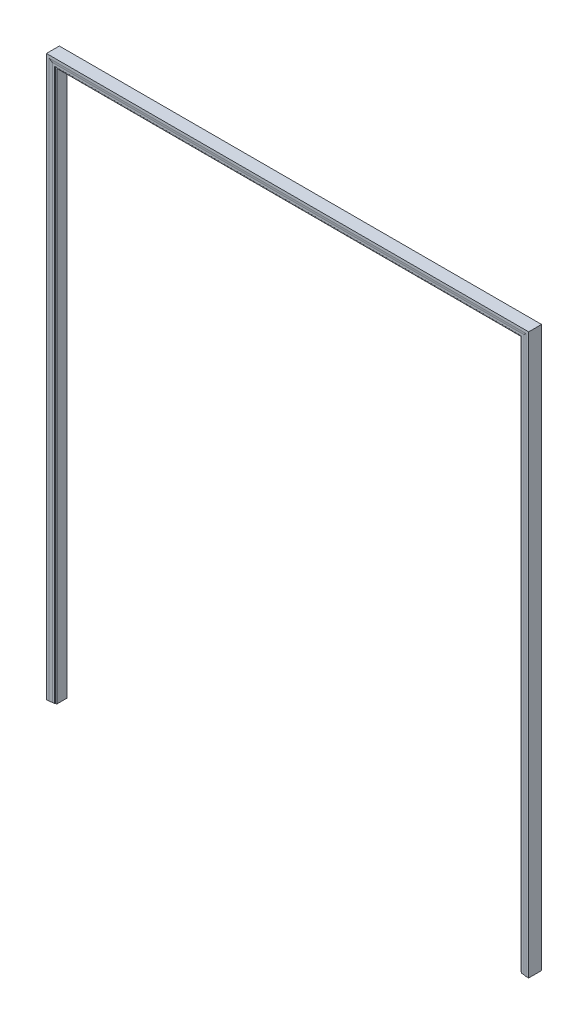
SolidWorks part; units mm, degrees
ref_plane "Front" through (0, 0, 0) normal (0, 0, 1) x (1, 0, 0)
ref_plane "Top" through (0, 0, 0) normal (0, 1, 0) x (1, 0, 0)
ref_plane "Right" through (0, 0, 0) normal (1, 0, 0) x (0, 0, -1)
sketch "Sketch1" plane through (0, 0, 0) normal (0, 0, 1) x (1, 0, 0)
  line L0 (-935, -1102.5) -> (-935, 1102.5)
  line L1 (-900, -1067.5) -> (900, -1067.5)
  line L2 (-900, -1067.5) -> (-900, 1067.5)
  line L3 (-900, 1067.5) -> (900, 1067.5)
  line L4 (900, -1067.5) -> (900, 1067.5)
  line L5 (-900, -1067.5) -> (900, 1067.5) construction
  line L6 (-900, 1067.5) -> (900, -1067.5) construction
  line L7 (-935, 1102.5) -> (935, 1102.5)
  line L8 (935, -1102.5) -> (935, 1102.5)
  line L9 (-935, -1102.5) -> (935, -1102.5)
  point P0 (0, 0)
  dimension "D1" = 2135
  dimension "D2" = 1800
  dimension "D3" = 35
extrude "Boss-Extrude1" add sketch "Sketch1" along normal mid plane 50
sketch "Sketch2" plane through (0, 0, 25) normal (0, 0, 1) x (1, 0, 0)
  line L8 (-905, -1072.5) -> (905, -1072.5)
  line L9 (905, -1072.5) -> (905, 1072.5)
  line L10 (905, 1072.5) -> (-905, 1072.5)
  line L11 (-905, 1072.5) -> (-905, -1072.5)
  line L12 (-905, -1072.5) -> (905, -1072.5)
  line L13 (905, -1072.5) -> (905, 1072.5)
  line L14 (905, 1072.5) -> (-905, 1072.5)
  line L15 (-905, 1072.5) -> (-905, -1072.5)
  dimension "D1" = 5
extrude "Cut-Extrude2" cut sketch "Sketch2" against normal blind 5
sketch "Sketch3" plane through (0, 0, 25) normal (0, 0, 1) x (1, 0, 0)
  line L8 (912.5, -1080) -> (912.5, 1080)
  line L9 (-912.5, -1080) -> (912.5, -1080)
  line L10 (-912.5, 1080) -> (-912.5, -1080)
  line L11 (912.5, 1080) -> (-912.5, 1080)
  line L12 (912.5, -1080) -> (912.5, 1080)
  line L13 (-912.5, -1080) -> (912.5, -1080)
  line L14 (-912.5, 1080) -> (-912.5, -1080)
  line L15 (912.5, 1080) -> (-912.5, 1080)
  dimension "D1" = 7.5
extrude "Cut-Extrude4" cut sketch "Sketch3" against normal blind 2
fillet "Fillet1" radius 1 4 edges at (905, 0, 23) (0, 1072.5, 23) (-905, 0, 23) (0, -1072.5, 23)
chamfer "Chamfer1" distance 12 angle 11 4 edges at (0, 1080, 25) (912.5, 0, 25) (0, -1080, 25) (-912.5, 0, 25) first distance on face at (0, 0, 25)
mirror "Mirror1" about plane through (0, 0, 0) normal (0, 0, 1) of "Cut-Extrude4", "Cut-Extrude2"
fillet "Fillet2" radius 1 4 edges at (-905, 0, -23) (0, -1072.5, -23) (905, 0, -23) (0, 1072.5, -23)
chamfer "Chamfer2" distance 12 angle 11 4 edges at (0, 1080, -25) (912.5, 0, -25) (-912.5, 0, -25) (0, -1080, -25) first distance on face at (0, 0, -25)
sketch "Sketch5" plane through (0, -1102.5, 0) normal (0, -1, 0) x (1, 0, 0)
  line L1 (-935, 25) -> (935, 25)
  line L2 (-935, 25) -> (-935, -25)
  line L3 (-935, -25) -> (935, -25)
  line L4 (935, 25) -> (935, -25)
extrude "Cut-Extrude5" cut sketch "Sketch5" against normal up to surface (35 mm away) up to face at (0, -1067.5, 0)
